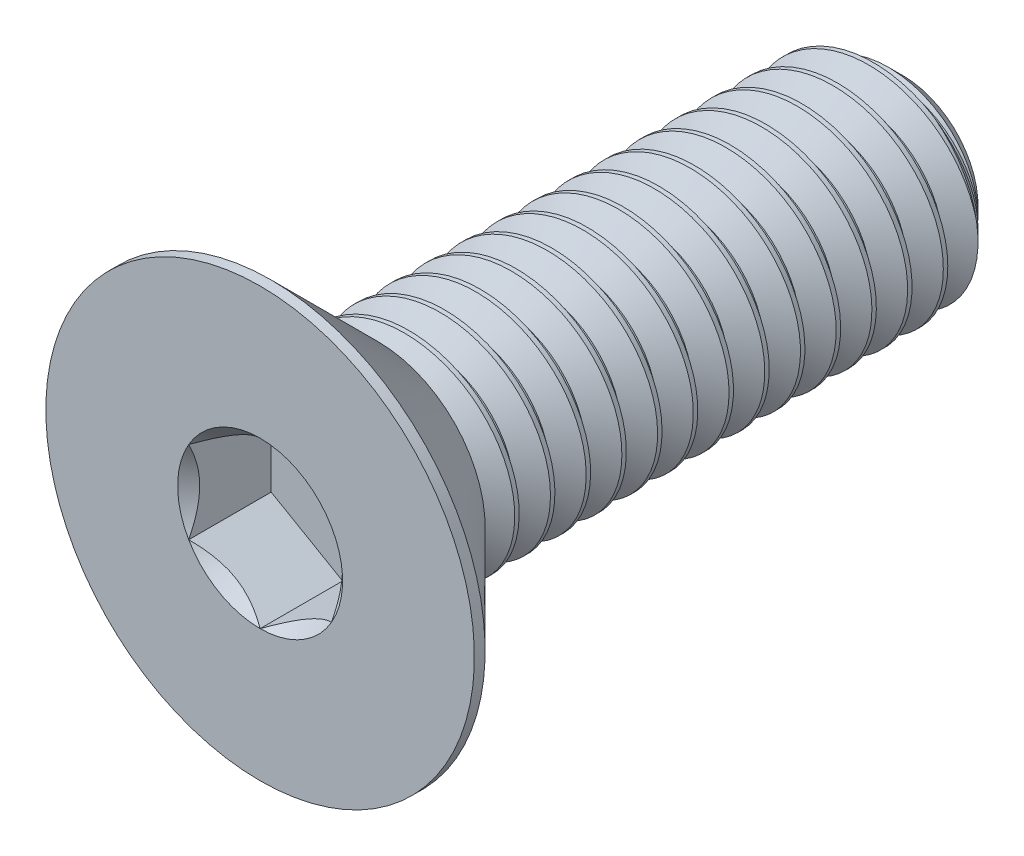
SolidWorks part; units mm, degrees
ref_plane "Front" through (0, 0, 0) normal (0, 0, 1) x (1, 0, 0)
ref_plane "Top" through (0, 0, 0) normal (0, 1, 0) x (1, 0, 0)
ref_plane "Right" through (0, 0, 0) normal (1, 0, 0) x (0, 0, -1)
sketch "Sketch1" plane through (0, 0, 0) normal (1, 0, 0) x (0, 0, -1)
  line L0 (-9, 6) -> (-8.7, 6) construction
  line L1 (-8.7, 6) -> (-5.7, 3) construction
  line L2 (-9, 3) -> (9, 3) construction
  line L3 (9, 3) -> (9, 0) construction
  line L4 (9, 0) -> (-9, 0) construction
  line L5 (-9, 0) -> (-9, 6) construction
  line L6 (-9, 6) -> (-9, -6) construction
  line L7 (9, 3) -> (9, -3) construction
  line L8 (-9, -6) -> (-8.7, -6) construction
  line L9 (-8.7, -6) -> (-5.7, -3) construction
  line L11 (-9, 3) -> (-9, 0) construction
  line L12 (-5.7, 3) -> (-5.7, 0) construction
  line L13 (8.9375, 3.1083) -> (9.4375, 2.2422) construction
  line L14 (9.4375, 2.2422) -> (9.9375, 3.1083) construction
  line L15 (9.9375, 3.1083) -> (8.9375, 3.1083) construction
  line L16 (9.4375, 3.1083) -> (9.4375, 3) construction
  line L17 (9.4375, 3) -> (9.4375, 2.3505) construction
  line L18 (9.4375, 2.3505) -> (9.4375, 2.2422) construction
  line L19 (9.4375, 3.0541) -> (9.9063, 3.0541) construction
  line L20 (9.4375, 3.0541) -> (8.9688, 3.0541) construction
  line L21 (9, 3) -> (9.875, 3) construction
  line L22 (9.375, 2.3505) -> (9.5, 2.3505) construction
  line L23 (9, -3) -> (-5.7, -3) construction
  point P10 (6.5, -3)
  point P24 (-5.7, 3)
  point P30 (0, 0)
  dimension "Head Diameter" = 12
  dimension "Head Height" = 3.3
  dimension "Length" = 18
  dimension "Countersink Angle" = 90
  dimension "Thread Pitch" = 1
  dimension "D2" = 0.125
  dimension "Minimum Thread Length" = 14.7
  dimension "Thread Size" = 6
  dimension "D1" = 2.5
sketch "Sketch2" plane through (0, 0, 0) normal (0, 0, 1) x (1, 0, 0)
  line L1 (0, 2.3094) -> (-2, 1.1547) construction
  line L2 (-2, 1.1547) -> (-2, -1.1547) construction
  line L3 (-2, -1.1547) -> (0, -2.3094) construction
  line L4 (0, -2.3094) -> (2, -1.1547) construction
  line L5 (2, -1.1547) -> (2, 1.1547) construction
  line L6 (2, 1.1547) -> (0, 2.3094) construction
  circle A0 centre (0, 0) radius 2 construction
  dimension "Drive Size" = 4
sketch "Sketch3" plane through (0, 0, 0) normal (1, 0, 0) x (0, 0, -1)
  line L0 (-9, 3) -> (9, 3)
  line L1 (9, 3) -> (9, 0)
  line L2 (9, 0) -> (-9, 0)
  line L3 (-9, 0) -> (-9, 3)
revolve "Revolve1" add sketch "Sketch3" angle 360 about L4
chamfer "Chamfer1" distance 0.9 angle 45 1 edges at (0, 3, -9)
sketch "Sketch6" plane through (0, 0, 0) normal (1, 0, 0) x (0, 0, -1)
  line L0 (-9, 6) -> (-8.7, 6)
  line L1 (-8.7, 6) -> (-5.7, 3)
  line L2 (-5.7, 3) -> (-5.7, 0)
  line L3 (-5.7, 0) -> (-9, 0)
  line L4 (-9, 0) -> (-9, 6)
revolve "Revolve2" add sketch "Sketch6" angle 360 about L4
sketch "Sketch8" plane through (0, 0, 9) normal (0, 0, 1) x (1, 0, 0)
  line L0 (0, 2.3094) -> (-2, 1.1547) construction
  line L1 (2, 1.1547) -> (0, 2.3094) construction
  line L2 (2, -1.1547) -> (2, 1.1547) construction
  line L3 (0, -2.3094) -> (2, -1.1547) construction
  line L4 (-2, 1.1547) -> (-2, -1.1547) construction
  line L5 (-2, -1.1547) -> (0, -2.3094) construction
  line L6 (0, 2.3094) -> (-2, 1.1547)
  line L7 (2, 1.1547) -> (0, 2.3094)
  line L8 (2, -1.1547) -> (2, 1.1547)
  line L9 (0, -2.3094) -> (2, -1.1547)
  line L10 (-2, 1.1547) -> (-2, -1.1547)
  line L11 (-2, -1.1547) -> (0, -2.3094)
extrude "Cut-Extrude1" cut sketch "Sketch8" against normal blind 2.31
sketch "Sketch9" plane through (0, 0, 9) normal (0, 0, 1) x (1, 0, 0)
  circle A0 centre (0, 0) radius 2.3094
extrude "Cut-Extrude2" cut sketch "Sketch9" against normal up to next (2.31 mm away) draft 45
ref_plane "Plane1" through (0, 0, 5.7) normal (0, 0, 1) x (1, 0, 0)
split "Split1" trim tools "Plane1" bodies to split 124 resulting bodies 126 127
sketch "Sketch4" plane through (0, 0, -9) normal (0, 0, -1) x (-1, 0, 0)
  circle A0 centre (0, 0) radius 3 construction
  circle A1 centre (0, 0) radius 3
curve "Helix/Spiral1" pitch 1 height 15.7 radius 3 centre (0, 0, -9) axis (0, 0, 1) start towards (0, 1, 0)
sketch "Sketch10" plane through (0, 0, 0) normal (1, 0, 0) x (0, 0, -1)
  line L0 (8.9688, 3.0541) -> (9.9063, 3.0541)
  line L1 (9.9063, 3.0541) -> (9.5, 2.3505)
  line L2 (9.5, 2.3505) -> (9.375, 2.3505)
  line L3 (9.375, 2.3505) -> (8.9688, 3.0541)
sweep "Cut-Sweep1" cut profiles "Sketch10" path "Helix/Spiral1"
equation "\"D2@Sketch1\" = \"Thread Pitch@Sketch1\" / 8"
equation "\"D4@Helix/Spiral1\"=\"Thread Pitch@Sketch1\""
equation "\"D3@Helix/Spiral1\"=\"Minimum Thread Length@Sketch1\"+\"Thread Pitch@Sketch1\""
equation "\"D1@Chamfer1\"=\"Thread Size@Sketch1\"*.15"
equation "\"D1@Cut-Extrude1\"=\"Head Height@Sketch1\"*.7"
equation "\"D1@Sketch1\"=\"Thread Pitch@Sketch1\"*2.5"
